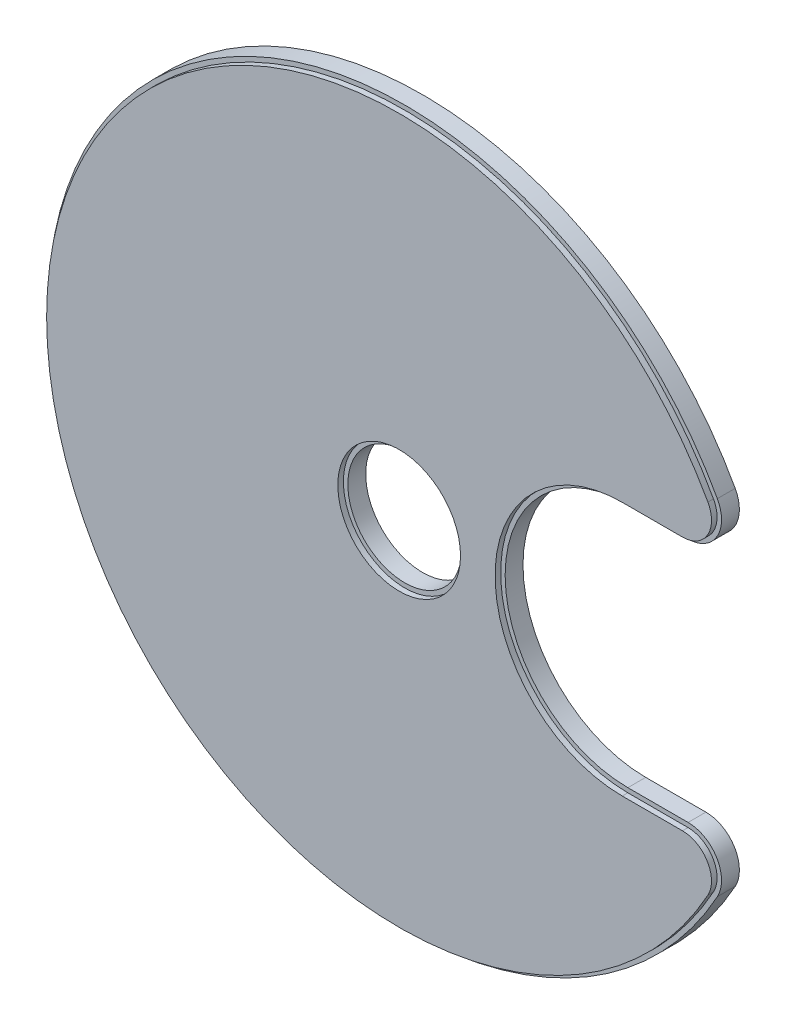
SolidWorks part; units mm, degrees
ref_plane "Plan de face" through (0, 0, 0) normal (0, 0, 1) x (1, 0, 0)
ref_plane "Plan de dessus" through (0, 0, 0) normal (0, 1, 0) x (1, 0, 0)
ref_plane "Plan de droite" through (0, 0, 0) normal (1, 0, 0) x (0, 0, -1)
sketch "Esquisse1" plane through (0, 0, 0) normal (0, 0, 1) x (1, 0, 0)
  line L0 (30.05, 11) -> (20, 11)
  line L1 (0, 0) -> (23.2256, 0) construction
  line L2 (30.05, -11) -> (20, -11)
  circle A0 centre (0, 0) radius 5.1
  arc A1 (20, 11) -> (20, -11) centre (20, 0) ccw
  arc A2 (30.05, 11) -> (30.05, -11) centre (0, 0) ccw
  dimension "D1" = 10.2
  dimension "D3" = 32
  dimension "D2" = 22
  dimension "D4" = 20
extrude "Boss.-Extru.1" add sketch "Esquisse1" along normal blind 1.6
fillet "Congé1" radius 3 2 edges at (30.05, -11, 0.8) (30.05, 11, 0.8)
sketch "Esquisse2" plane through (0, 0, 1.6) normal (0, 0, 1) x (1, 0, 0)
  line L4 (25.3969, -11.4) -> (20, -11.4)
  line L5 (20, 11.4) -> (25.3969, 11.4)
  line L6 (25.3969, -11.4) -> (20, -11.4)
  line L7 (20, 11.4) -> (25.3969, 11.4)
  circle A6 centre (0, 0) radius 5.5
  circle A7 centre (0, 0) radius 5.5
  arc A8 (25.3969, 11.4) -> (27.6738, 15.2552) centre (25.3969, 14) ccw
  arc A9 (27.6738, 15.2552) -> (27.6738, -15.2552) centre (0, 0) ccw
  arc A10 (27.6738, -15.2552) -> (25.3969, -11.4) centre (25.3969, -14) ccw
  arc A11 (20, 11.4) -> (20, -11.4) centre (20, 0) ccw
  arc A12 (25.3969, 11.4) -> (27.6738, 15.2552) centre (25.3969, 14) ccw
  arc A13 (27.6738, 15.2552) -> (27.6738, -15.2552) centre (0, 0) ccw
  arc A14 (27.6738, -15.2552) -> (25.3969, -11.4) centre (25.3969, -14) ccw
  arc A15 (20, 11.4) -> (20, -11.4) centre (20, 0) ccw
  dimension "D1" = 0.4
  dimension "D2" = 0.4
extrude "Boss.-Extru.2" add sketch "Esquisse2" along normal blind 0.5
